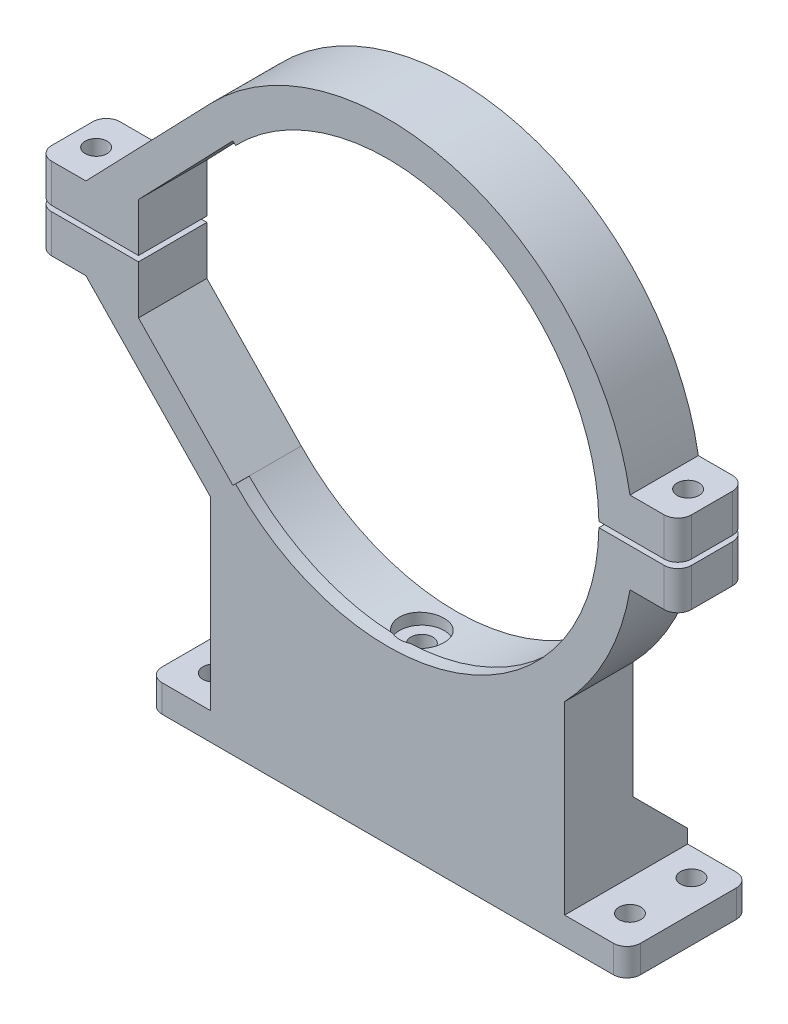
SolidWorks part; units mm, degrees
ref_plane "Front Plane" through (0, 0, 0) normal (0, 0, 1) x (1, 0, 0)
ref_plane "Top Plane" through (0, 0, 0) normal (0, 1, 0) x (1, 0, 0)
ref_plane "Right Plane" through (0, 0, 0) normal (1, 0, 0) x (0, 0, -1)
sketch "Sketch1" plane through (0, 0, 0) normal (0, 0, 1) x (1, 0, 0)
  line L0 (-35.95, 0) -> (35.95, 0) construction
  line L1 (-35.4458, 6) -> (35.4458, 6) construction
  line L2 (-35.4458, -6) -> (35.4458, -6) construction
  line L3 (35.4458, -6) -> (42.4458, -6)
  line L4 (42.4458, -6) -> (42.4458, 6)
  line L5 (42.4458, 6) -> (35.4458, 6)
  line L6 (-25.8855, 24.9468) -> (-44.1452, 6)
  line L7 (-44.1452, 6) -> (-51.1452, 6)
  line L8 (-51.1452, 6) -> (-51.1452, -6)
  line L9 (-51.1452, -6) -> (-44.1452, -6)
  line L10 (-44.1452, -6) -> (-25.8855, -24.9468)
  line L11 (-22.6453, 21.8241) -> (-36.45, 7.5)
  line L12 (-36.45, 7.5) -> (-36.45, -7.5)
  line L13 (-36.45, -7.5) -> (-22.6453, -21.8241)
  line L14 (-36.45, 0) -> (-51.1452, 0) construction
  line L15 (-25.8855, -24.9468) -> (-25.8855, -55.99)
  line L16 (-25.8855, -55.99) -> (25.8855, -55.99)
  line L17 (25.8855, -55.99) -> (25.8855, -24.9468)
  line L18 (-25.8855, -24.9468) -> (25.8855, -24.9468) construction
  circle A0 centre (0, 0) radius 31.45
  circle A1 centre (0, 0) radius 35.95
  dimension "D1" = 62.9
  dimension "D2" = 4.5
  dimension "D3" = 6
  dimension "D4" = 6
  dimension "D5" = 5
  dimension "D6" = 15
  dimension "D7" = 7
  dimension "D8" = 20.04
extrude "Boss-Extrude1" add sketch "Sketch1" along normal blind 10 contours A1 L6 L7 L8 L9 L10 L13 L12 L11 | A1 L11 A0 L13 | A1 L15 L16 L17 | A1 L3 L4 L5
sketch "Sketch2" plane through (0, 0, 10) normal (0, 0, 1) x (1, 0, 0)
  line L0 (-36.45, -7.5) -> (-22.6453, -21.8241) construction
  line L1 (-22.6453, 21.8241) -> (-36.45, 7.5) construction
  line L2 (-36.45, -7.5) -> (-22.6453, -21.8241)
  line L3 (-22.6453, 21.8241) -> (-36.45, 7.5)
  line L4 (-22.6453, 21.8241) -> (0, 0)
  line L5 (0, 0) -> (-22.6453, -21.8241)
  circle A0 centre (0, 0) radius 30.9
  arc A1 (-22.6453, -21.8241) -> (-22.6453, 21.8241) centre (0, 0) ccw construction
  arc A2 (-22.6453, -21.8241) -> (-22.6453, 21.8241) centre (0, 0) ccw
  arc M3 (-22.6453, 21.8241) -> (-22.6453, -21.8241) centre (0, 0) cw
  dimension "D1" = 61.8
extrude "Boss-Extrude2" add sketch "Sketch2" against normal blind 2 contours A0 L5 L4 M3
sketch "Sketch3" plane through (0, 0, 10) normal (0, 0, 1) x (1, 0, 0)
  line L1 (-56.2857, -0.4) -> (56.2857, -0.4)
  line L2 (-56.2857, -0.4) -> (-56.2857, 0.4)
  line L3 (-56.2857, 0.4) -> (56.2857, 0.4)
  line L4 (56.2857, -0.4) -> (56.2857, 0.4)
  line L5 (-56.2857, -0.4) -> (56.2857, 0.4) construction
  line L6 (-56.2857, 0.4) -> (56.2857, -0.4) construction
  point P0 (0, 0)
  dimension "D1" = 0.8
extrude "Cut-Extrude1" cut sketch "Sketch3" against normal through all
sketch "Sketch4" plane through (0, -55.99, 0) normal (0, -1, 0) x (1, 0, 0)
  line L0 (-25.8855, 5) -> (25.8855, 5) construction
  line L1 (-25.8855, 10) -> (-25.8855, 0) construction
  line L2 (25.8855, 10) -> (25.8855, 0) construction
  line L3 (-17.5, 5) -> (0, 0) construction
  line L4 (0, 0) -> (17.5, 5) construction
  circle A0 centre (-17.5, 5) radius 1.55
  circle A1 centre (17.5, 5) radius 1.55
  dimension "D1" = 3.1
  dimension "D2" = 35
extrude "Cut-Extrude2" cut sketch "Sketch4" against normal blind 10
sketch "Sketch5" plane through (0, 6, 0) normal (0, 1, 0) x (1, 0, 0)
  line L0 (-51.1452, -5) -> (42.4458, -5) construction
  line L1 (-51.1452, -10) -> (-51.1452, 0) construction
  line L2 (42.4458, -10) -> (42.4458, 0) construction
  line L3 (-47.6452, 0) -> (-47.6452, -10) construction
  line L4 (-44.1452, 0) -> (-51.1452, 0) construction
  line L5 (-44.1452, -10) -> (-51.1452, -10) construction
  line L6 (0, 0) -> (0, -10) construction
  line L7 (-25.8855, -10) -> (35.4458, -10) construction
  line L8 (38.9458, 0) -> (38.9458, -10) construction
  line L9 (42.4458, 0) -> (35.4458, 0) construction
  line L10 (42.4458, -10) -> (35.4458, -10) construction
  circle A0 centre (-47.6452, -5) radius 1.6
  circle A2 centre (38.9458, -5) radius 1.6
  dimension "D1" = 3.2
extrude "Cut-Extrude3" cut sketch "Sketch5" against normal through all
fillet "Fillet1" radius 2 4 edges at (-51.1452, 3.2, 0) (-51.1452, 3.2, 10) (42.4458, 3.2, 0) (42.4458, 3.2, 10)
fillet "Fillet2" radius 2 4 edges at (-51.1452, -3.2, 10) (-51.1452, -3.2, 0) (42.4458, -3.2, 10) (42.4458, -3.2, 0)
sketch "Sketch6" plane through (0, -55.99, 0) normal (0, -1, 0) x (1, 0, 0)
  line L0 (-25.8855, 10) -> (-35, 10)
  line L1 (-35, 10) -> (-35, -8)
  line L2 (-35, -8) -> (35, -8)
  line L3 (35, -8) -> (35, 10)
  line L4 (-25.8855, 0) -> (25.8855, 0)
  line L5 (25.8855, 0) -> (25.8855, 10)
  line L6 (25.8855, 10) -> (-25.8855, 10)
  line L7 (-25.8855, 10) -> (-25.8855, 0)
  line L8 (-25.8855, 0) -> (25.8855, 0)
  line L9 (25.8855, 0) -> (25.8855, 10)
  line L10 (25.8855, 10) -> (-25.8855, 10)
  line L11 (-25.8855, 10) -> (-25.8855, 0)
  line L12 (35, 10) -> (25.8855, 10)
  line L13 (25.8855, 5) -> (35, 5) construction
  line L14 (0, 0) -> (0, -8) construction
  line L15 (0, -4) -> (35, -4) construction
  line L16 (30.4427, 5) -> (30.4427, -4) construction
  circle A0 centre (30.4427, 5) radius 1.6
  circle A1 centre (30.4427, -4) radius 1.6
  circle A2 centre (-30.4427, 5) radius 1.6
  circle A3 centre (-30.4427, -4) radius 1.6
  line M12 (-25.8855, 0) -> (25.8855, 0)
  line M13 (25.8855, 0) -> (25.8855, 10)
  line M15 (-25.8855, 10) -> (-25.8855, 0)
  dimension "D4" = 3.2
  dimension "D2" = 70
  dimension "D3" = 18
  dimension "D1" = 0
extrude "Boss-Extrude3" add sketch "Sketch6" against normal blind 4 contours L3 L12 L0 L1 L2 A2 A1 A0 A3 M13 M12 M15
fillet "Fillet3" radius 2 4 edges at (-35, -53.99, 10) (-35, -53.99, -8) (35, -53.99, -8) (35, -53.99, 10)
chamfer "Chamfer1" distance 10 angle 45 1 edges at (0, -51.99, 0)
sketch "Sketch7" plane through (0, -55.99, 0) normal (0, -1, 0) x (1, 0, 0)
  line L0 (-30.4427, 5) -> (30.4427, 5) construction
  circle A0 centre (0, 5) radius 1.6
  dimension "D1" = 3.2
extrude "Cut-Extrude4" cut sketch "Sketch7" against normal blind 49
sketch "Sketch8" plane through (0, 0, 0) normal (0, 1, 0) x (1, 0, 0)
  circle A0 centre (0, -5) radius 1.6 construction
  circle A1 centre (0, -5) radius 1.6 construction
  circle A2 centre (0, -5) radius 3.25
  dimension "D1" = 6.5
extrude "Cut-Extrude5" cut sketch "Sketch8" against normal blind 33
